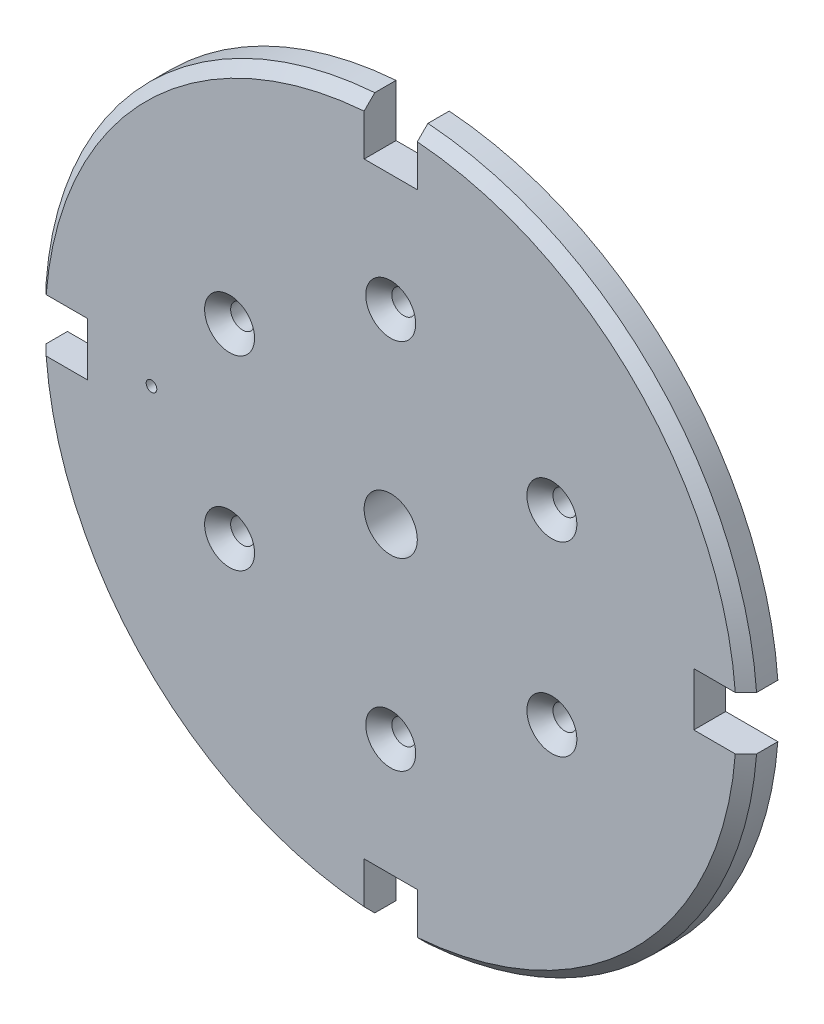
SolidWorks part; units mm, degrees
material "7075-T6 (SN)"
ref_plane "Płaszczyzna przednia" through (0, 0, 0) normal (0, 0, 1) x (1, 0, 0)
ref_plane "Płaszczyzna górna" through (0, 0, 0) normal (0, 1, 0) x (1, 0, 0)
ref_plane "Płaszczyzna prawa" through (0, 0, 0) normal (1, 0, 0) x (0, 0, -1)
sketch "Szkic1" plane through (0, 0, 0) normal (0, 0, 1) x (1, 0, 0)
  circle A0 centre (0, 0) radius 67
  dimension "D1" = 134
extrude "Dodanie-wyciągnięcie1" add sketch "Szkic1" along normal blind 6
chamfer "Sfazowanie1" distance 2 1 edges at (67, 0, 6)
sketch "Szkic2" plane through (0, 0, 6) normal (0, 0, 1) x (1, 0, 0)
  line L0 (0, 12.06) -> (0, 0) construction
  line L1 (0, 0) -> (4.6152, 11.142) construction
  circle A1 centre (0, 0) radius 12.06
  circle A3 centre (0, 0) radius 4.25 construction
  circle A4 centre (0, 0) radius 5.5 construction
  circle A5 centre (0, 0) radius 9 construction
  circle A7 centre (0, 0) radius 7.5 construction
  circle A8 centre (0, 0) radius 10.5 construction
  circle A9 centre (0, 0) radius 24.12 construction
  circle A11 centre (0, 0) radius 2.5 construction
  point P12 (0, 2.5)
  point P13 (0, 0)
  point P14 (0, 0)
  point P16 (0, 5.5)
  point P18 (0, 9)
  point P20 (1.6264, 3.9265)
  point P21 (2.8701, 6.9291)
  point P22 (4.0182, 9.7007)
  dimension "D1" = 24.12
  dimension "D2" = 22.5
  dimension "D3" = 8.5
  dimension "D4" = 11
  dimension "D5" = 18
  dimension "D6" = 21
  dimension "D7" = 15
  dimension "D8" = 48.24
  dimension "D9" = 5
ref_axis "Oś1" through (0, 0, 12.2009) along (0, 0, -1)
hole_wizard "Otwory ustalające Ø10.0mm1" positions "Szkic3" profile "Szkic4" hole size "Ø10.0" standard "ISO"
sketch "Szkic3" plane through (0, 0, 6) normal (0, 0, 1) x (1, 0, 0)
  point P0 (0, 0)
sketch "Szkic4" plane through (0, 0, 6) normal (1, 0, 0) x (0, -1, 0)
  line L0 (0, 0) -> (0, 9.0043)
  line L1 (0, 9.0043) -> (5, 6)
  line L2 (5, 6) -> (5, 0)
  line L5 (5, 0) -> (0, 0)
  line L10 (0, 9.0043) -> (-5, 6) construction
  line L11 (0, -6.35) -> (0, 107.95) construction
  dimension "Średnica otworu" = 10
  dimension "Głębokość otworu" = 6
  dimension "Kąt wiertła" = 118
sketch "Szkic7" plane through (0, 0, 6) normal (0, 0, 1) x (1, 0, 0)
  circle A0 centre (0, 0) radius 35 construction
  circle A1 centre (0, 35) radius 2.05
  dimension "D1" = 70
  dimension "D2" = 4.1
extrude "Wytnij-wyciągnięcie1" cut sketch "Szkic7" against normal up to next
pattern_circular "Szyk kołowy2" count 6 over 360 about axis through (0, 0, 12.2009) along (0, 0, -1) of "Wytnij-wyciągnięcie1"
ref_plane "Płaszczyzna2" through (0, 0, 6) normal (0, 0, 1) x (1, 0, 0)
sketch "Szkic8" plane through (0, 0, 6) normal (0, 0, 1) x (1, 0, 0)
  line L1 (-65, 0) -> (65, 0) construction
  circle A0 centre (0, 0) radius 65 construction
  circle A1 centre (-45, 0) radius 1
  dimension "D2" = 2
  dimension "D4" = 45
extrude "Wytnij-wyciągnięcie2" cut sketch "Szkic8" against normal mid plane 40 contours A1
sketch "Szkic9" plane through (0, 0, 6) normal (0, 0, 1) x (1, 0, 0)
  line L0 (-65, 0) -> (65, 0) construction
  line L1 (57, 5) -> (67, 5)
  line L2 (57, 5) -> (57, -5)
  line L3 (57, -5) -> (67, -5)
  line L4 (67, 5) -> (67, -5)
  circle A0 centre (0, 0) radius 67 construction
  point P4 (57, 0)
  dimension "D1" = 10
  dimension "D2" = 10
extrude "Wytnij-wyciągnięcie3" cut sketch "Szkic9" against normal blind 10
pattern_circular "Szyk kołowy3" count 4 over 360 about axis through (0, 0, 6) along (0, 0, 1) of "Wytnij-wyciągnięcie3"
hole_wizard "Pogłębienie stożkowe pod M4 wkręt do części metalowych z łbem soczewkowym1" positions "Szkic 3D5" profile "Szkic14" countersink size "M4" standard "Ansi Metric" end condition through all
sketch3d "Szkic 3D5"
  circle A0 centre (0, 35, 6) radius 2.05 construction
  point P0 (0, 35, 6)
  point P6 (0, 35, 8.05)
  dimension "D1" = 35.5106
sketch "Szkic14" plane through (0, 35, 6) normal (1, 0, 0) x (0, -1, 0)
  line L0 (0, 0) -> (0, 6)
  line L1 (0, 6) -> (2.25, 6)
  line L2 (2.25, 6) -> (2.25, 2.45)
  line L3 (2.25, 2.45) -> (4.7, 0)
  line L5 (4.7, 0) -> (0, 0)
  line L6 (-2.25, 2.45) -> (-4.7, 0) construction
  line L11 (0, -6.35) -> (0, 107.95) construction
  dimension "Średnica otworu na wylot" = 4.5
  dimension "Głębokość otworu na wylot" = 6
  dimension "Średnica zewnętrznego pogłębienia stożkowego" = 9.4
  dimension "Kąt zewnętrznego pogłębienia stożkowego" = 90
pattern_circular "Szyk kołowy4" count 6 over 360 about axis through (0, 0, 12.2009) along (0, 0, -1) of "Pogłębienie stożkowe pod M4 wkręt do części metalowych z łbem soczewkowym1"
sketch "Szkic15" plane through (0, 0, 0) normal (0, 0, -1) x (-1, 0, 0)
  circle A0 centre (0, 0) radius 5
  circle A1 centre (0, 0) radius 9
  dimension "D1" = 10
  dimension "D2" = 18
extrude "Dodanie-wyciągnięcie2" add sketch "Szkic15" along normal blind 15
sketch "Szkic16" plane through (0, 0, 0) normal (0, 1, 0) x (1, 0, 0)
  line L0 (9, 15) -> (-9, 15) construction
  line L1 (-9, 15) -> (-9, 0) construction
  line L2 (0, -12.2009) -> (0, 6.0438) construction
  circle A0 centre (-4, 10) radius 0.75
  circle A1 centre (-4, 5) radius 0.75
  point P8 (-4, 5.0303)
  point P9 (0, 0)
  dimension "D1" = 5
  dimension "D3" = 1.5
  dimension "D5" = 1.5
  dimension "D2" = 5
  dimension "D4" = 5
  dimension "D6" = 4
extrude "Wytnij-wyciągnięcie4" cut sketch "Szkic16" along normal up to surface (8.0623 mm away) up to face at (-9, 0, -15)
pattern_circular "Szyk kołowy5" count 6 over 360 about axis through (0, 0, 12.2009) along (0, 0, -1) of "Wytnij-wyciągnięcie4"
sketch "Szkic17" plane through (0, 0, 0) normal (-1, 0, 0) x (0, 1, 0)
  line L0 (-9, 15) -> (-9, 0) construction
  line L1 (9, 15) -> (-9, 15) construction
  line L3 (0, -12.2009) -> (0, 6.0438) construction
  circle A0 centre (-4, 7.5) radius 0.75
  circle A1 centre (-4, 2.5) radius 0.75
  point P4 (-4.1244, 3.1711)
  point P9 (-4, 3.2235)
  dimension "D1" = 1.5
  dimension "D4" = 1.5
  dimension "D2" = 7.5
  dimension "D3" = 5
  dimension "D5" = 4
  dimension "D6" = 5
extrude "Wytnij-wyciągnięcie5" cut sketch "Szkic17" along normal up to surface (8.0623 mm away) up to face at (-9, 0, -15)
pattern_circular "Szyk kołowy6" count 6 over 360 about axis through (0, 0, 12.2009) along (0, 0, -1) of "Wytnij-wyciągnięcie5"
